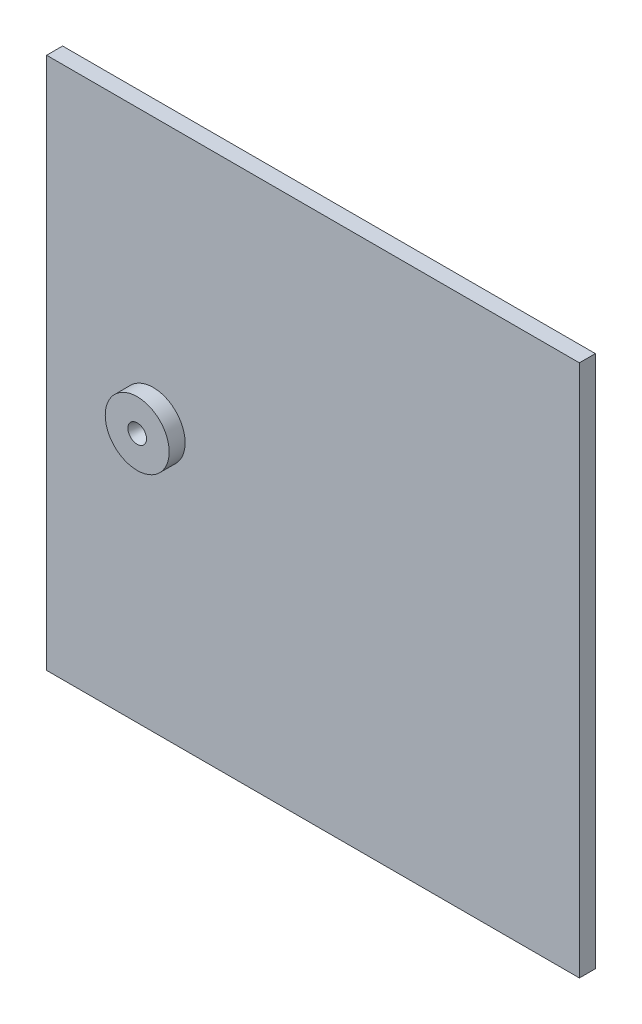
SolidWorks part; units mm, degrees
ref_plane "Front Plane" through (0, 0, 0) normal (0, 0, 1) x (1, 0, 0)
ref_plane "Top Plane" through (0, 0, 0) normal (0, 1, 0) x (1, 0, 0)
ref_plane "Right Plane" through (0, 0, 0) normal (1, 0, 0) x (0, 0, -1)
sketch "Sketch1" plane through (0, 0, 0) normal (0, 0, 1) x (1, 0, 0)
  line L1 (0, 0) -> (100, 0)
  line L2 (0, 0) -> (0, 100)
  line L3 (0, 100) -> (100, 100)
  line L4 (100, 0) -> (100, 100)
  dimension "D1" = 100
extrude "Boss-Extrude1" add sketch "Sketch1" along normal blind 3
sketch "Sketch2" plane through (0, 0, 3) normal (0, 0, 1) x (1, 0, 0)
  line L0 (0, 50) -> (20, 50) construction
  line L1 (0, 100) -> (0, 0) construction
  circle A0 centre (20, 50) radius 6.25
  dimension "D1" = 12.5
  dimension "D3" = 20
extrude "Boss-Extrude2" add sketch "Sketch2" against normal blind 30
sketch "Sketch3" plane through (0, 0, -27) normal (0, 0, -1) x (-1, 0, 0)
  circle A0 centre (-20, 50) radius 0.75
  dimension "D1" = 1.5
extrude "Cut-Extrude1" cut sketch "Sketch3" against normal through all
sketch "Sketch4" plane through (0, 0, 3) normal (0, 0, 1) x (1, 0, 0)
  circle A0 centre (20, 50) radius 6
  circle A1 centre (20, 50) radius 0.75 construction
  circle A2 centre (20, 50) radius 0.75
  dimension "D1" = 12
extrude "Boss-Extrude3" add sketch "Sketch4" along normal blind 3
chamfer "Chamfer1" distance 1 distance2 3 2 edges at (20.75, 50, 6) (19.25, 50, -27) first distance on face at (26, 50, 6) first distance on face at (19.25, 50, -27)
